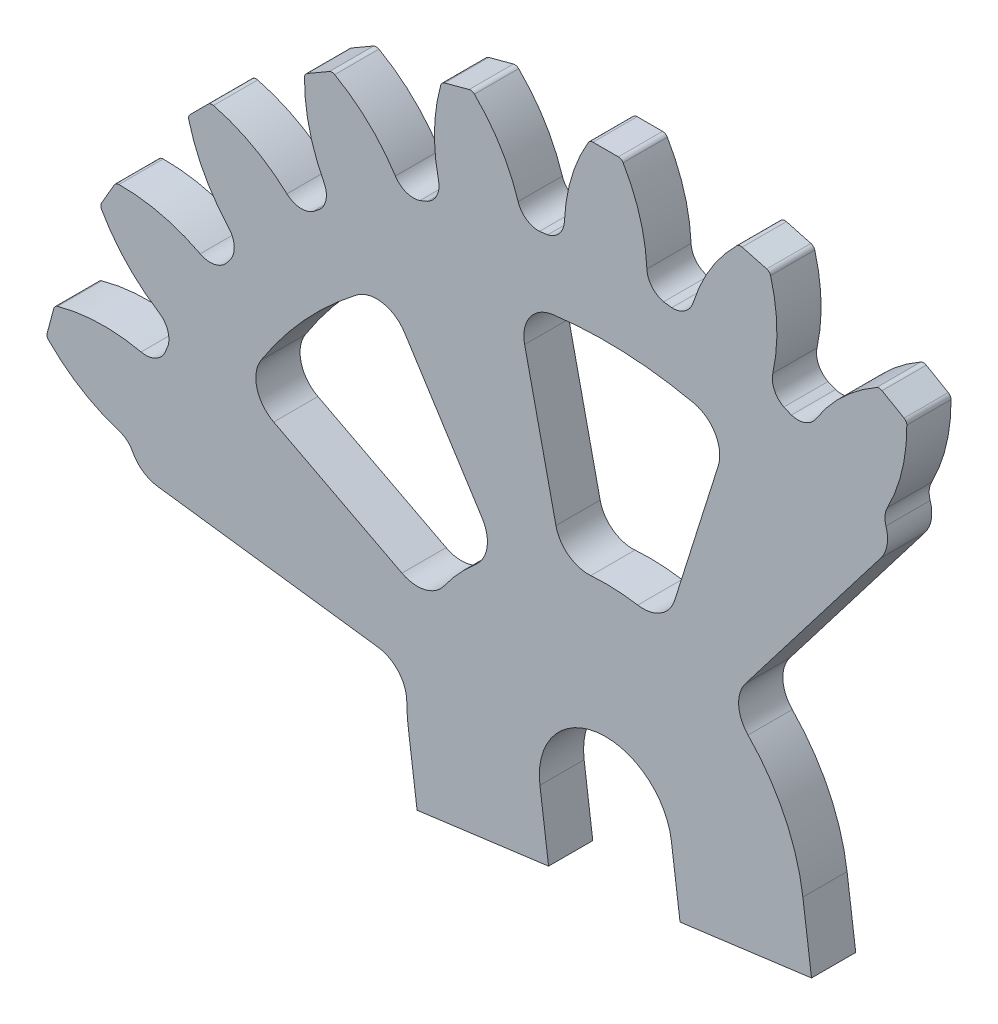
SolidWorks part; units mm, degrees
note: '?' marks a value the reader was unsure of.
ref_plane "Front" through (0, 0, 0) normal (0, 0, 1) x (1, 0, 0)
ref_plane "Top" through (0, 0, 0) normal (0, 1, 0) x (1, 0, 0)
ref_plane "Right" through (0, 0, 0) normal (1, 0, 0) x (0, 0, -1)
sketch "Sketch1" plane through (0, 0, 0) normal (0, 0, 1) x (1, 0, 0)
  line L0 (17.8313, 135.4426) -> (17.1518, 135.5303)
  line L1 (17.1518, 135.5303) -> (16.4718, 135.6147)
  line L2 (16.4718, 135.6147) -> (16.2604, 135.6453)
  line L3 (16.2604, 135.6453) -> (16.051, 135.6853)
  line L4 (16.051, 135.6853) -> (15.8446, 135.7346)
  line L5 (15.8446, 135.7346) -> (15.6419, 135.7926)
  line L6 (15.6419, 135.7926) -> (15.4439, 135.859)
  line L7 (15.4439, 135.859) -> (15.2509, 135.9332)
  line L8 (15.2509, 135.9332) -> (15.0638, 136.0145)
  line L9 (15.0638, 136.0145) -> (14.8827, 136.1025)
  line L10 (14.8827, 136.1025) -> (14.7082, 136.1963)
  line L11 (14.7082, 136.1963) -> (14.5404, 136.2955)
  line L12 (14.5404, 136.2955) -> (14.3796, 136.3992)
  line L13 (14.3796, 136.3992) -> (14.2256, 136.507)
  line L14 (14.2256, 136.507) -> (14.0785, 136.6183)
  line L15 (14.0785, 136.6183) -> (13.9383, 136.7325)
  line L16 (13.9383, 136.7325) -> (13.8047, 136.8493)
  line L17 (13.8047, 136.8493) -> (13.6777, 136.9682)
  line L18 (13.6777, 136.9682) -> (13.5568, 137.0887)
  line L19 (13.5568, 137.0887) -> (13.442, 137.2107)
  line L20 (13.442, 137.2107) -> (13.333, 137.3338)
  line L21 (13.333, 137.3338) -> (13.2295, 137.4577)
  line L22 (13.2295, 137.4577) -> (13.1311, 137.5824)
  line L23 (13.1311, 137.5824) -> (13.0378, 137.7076)
  line L24 (13.0378, 137.7076) -> (12.9491, 137.8333)
  line L25 (12.9491, 137.8333) -> (12.8649, 137.9592)
  line L26 (12.8649, 137.9592) -> (12.7848, 138.0855)
  line L27 (12.7848, 138.0855) -> (12.7088, 138.2119)
  line L28 (12.7088, 138.2119) -> (12.6364, 138.3386)
  line L29 (12.6364, 138.3386) -> (12.5676, 138.4654)
  line L30 (12.5676, 138.4654) -> (12.4399, 138.7196)
  line L31 (12.4399, 138.7196) -> (12.324, 138.9746)
  line L32 (12.324, 138.9746) -> (12.2189, 139.2306)
  line L33 (12.2189, 139.2306) -> (12.1235, 139.488)
  line L34 (12.1235, 139.488) -> (12.037, 139.7472)
  line L35 (12.037, 139.7472) -> (11.9587, 140.0083)
  line L36 (11.9587, 140.0083) -> (11.8878, 140.272)
  line L37 (11.8878, 140.272) -> (11.8239, 140.5386)
  line L38 (11.8239, 140.5386) -> (11.7667, 140.8083)
  line L39 (11.7667, 140.8083) -> (11.7159, 141.0816)
  line L40 (11.7159, 141.0816) -> (11.671, 141.3588)
  line L41 (11.671, 141.3588) -> (11.6319, 141.6402)
  line L42 (11.6319, 141.6402) -> (11.5986, 141.9261)
  line L43 (11.5986, 141.9261) -> (11.5708, 142.2169)
  line L44 (11.5708, 142.2169) -> (11.5484, 142.5127)
  line L45 (11.5484, 142.5127) -> (11.5316, 142.8138)
  line L46 (11.5316, 142.8138) -> (11.5201, 143.1205)
  line L47 (11.5201, 143.1205) -> (11.514, 143.431)
  line L48 (11.514, 143.431) -> (11.5065, 143.7657)
  line L49 (11.5065, 143.7657) -> (11.492, 144.1009)
  line L50 (11.492, 144.1009) -> (11.4715, 144.4366)
  line L51 (11.4715, 144.4366) -> (11.4457, 144.7727)
  line L52 (11.4457, 144.7727) -> (11.415, 145.1092)
  line L53 (11.415, 145.1092) -> (11.3797, 145.4459)
  line L54 (11.3797, 145.4459) -> (11.3401, 145.783)
  line L55 (11.3401, 145.783) -> (11.2966, 146.1204)
  line L56 (11.2966, 146.1204) -> (11.2492, 146.458)
  line L57 (11.2492, 146.458) -> (11.1981, 146.7959)
  line L58 (11.1981, 146.7959) -> (11.1435, 147.1341)
  line L59 (11.1435, 147.1341) -> (11.0853, 147.4724)
  line L60 (11.0853, 147.4724) -> (11.024, 147.8109)
  line L61 (11.024, 147.8109) -> (10.9594, 148.1496)
  line L62 (10.9594, 148.1496) -> (10.8916, 148.4885)
  line L63 (10.8916, 148.4885) -> (10.8208, 148.8275)
  line L64 (10.8208, 148.8275) -> (10.6703, 149.5062)
  line L65 (10.6703, 149.5062) -> (10.5084, 150.1852)
  line L66 (10.5084, 150.1852) -> (10.3354, 150.8648)
  line L67 (10.3354, 150.8648) -> (10.1517, 151.5448)
  line L68 (10.1517, 151.5448) -> (9.9576, 152.2251)
  line L69 (9.9576, 152.2251) -> (9.7535, 152.9057)
  line L70 (9.7535, 152.9057) -> (9.5395, 153.5865)
  line L71 (9.5395, 153.5865) -> (9.3158, 154.2674)
  line L72 (9.3158, 154.2674) -> (9.0828, 154.9485)
  line L73 (9.0828, 154.9485) -> (8.8405, 155.6295)
  line L74 (8.8405, 155.6295) -> (8.589, 156.3106)
  line L75 (8.589, 156.3106) -> (8.3286, 156.9917)
  line L76 (8.3286, 156.9917) -> (8.0594, 157.6726)
  line L77 (8.0594, 157.6726) -> (7.7815, 158.3534)
  line L78 (7.7815, 158.3534) -> (7.4951, 159.0339)
  line L79 (7.4951, 159.0339) -> (7.2001, 159.7142)
  line L80 (7.2001, 159.7142) -> (6.8968, 160.3942)
  line L81 (6.8968, 160.3942) -> (6.5852, 161.0739)
  line L82 (6.5852, 161.0739) -> (6.2654, 161.7531)
  line L83 (6.2654, 161.7531) -> (5.9375, 162.432)
  line L84 (5.9375, 162.432) -> (5.6015, 163.1103)
  line L85 (5.6015, 163.1103) -> (5.2576, 163.7881)
  line L86 (5.2576, 163.7881) -> (4.9057, 164.4653)
  line L87 (4.9057, 164.4653) -> (4.5461, 165.1419)
  line L88 (4.5461, 165.1419) -> (3.4097, 165.1693)
  line L89 (3.4097, 165.1693) -> (2.2732, 165.1888)
  line L90 (2.2732, 165.1888) -> (1.1366, 165.2006)
  line L91 (1.1366, 165.2006) -> (0, 165.2045)
  line L92 (0, 165.2045) -> (-1.1366, 165.2006)
  line L93 (-1.1366, 165.2006) -> (-2.2732, 165.1888)
  line L94 (-2.2732, 165.1888) -> (-3.4097, 165.1693)
  line L95 (-3.4097, 165.1693) -> (-4.5461, 165.1419)
  line L96 (-4.5461, 165.1419) -> (-4.9057, 164.4653)
  line L97 (-4.9057, 164.4653) -> (-5.2576, 163.7881)
  line L98 (-5.2576, 163.7881) -> (-5.6015, 163.1103)
  line L99 (-5.6015, 163.1103) -> (-5.9375, 162.432)
  line L100 (-5.9375, 162.432) -> (-6.2654, 161.7531)
  line L101 (-6.2654, 161.7531) -> (-6.5852, 161.0739)
  line L102 (-6.5852, 161.0739) -> (-6.8968, 160.3942)
  line L103 (-6.8968, 160.3942) -> (-7.2001, 159.7142)
  line L104 (-7.2001, 159.7142) -> (-7.4951, 159.0339)
  line L105 (-7.4951, 159.0339) -> (-7.7815, 158.3534)
  line L106 (-7.7815, 158.3534) -> (-8.0594, 157.6726)
  line L107 (-8.0594, 157.6726) -> (-8.3286, 156.9917)
  line L108 (-8.3286, 156.9917) -> (-8.589, 156.3106)
  line L109 (-8.589, 156.3106) -> (-8.8405, 155.6295)
  line L110 (-8.8405, 155.6295) -> (-9.0828, 154.9485)
  line L111 (-9.0828, 154.9485) -> (-9.3158, 154.2674)
  line L112 (-9.3158, 154.2674) -> (-9.5395, 153.5865)
  line L113 (-9.5395, 153.5865) -> (-9.7535, 152.9057)
  line L114 (-9.7535, 152.9057) -> (-9.9576, 152.2251)
  line L115 (-9.9576, 152.2251) -> (-10.1517, 151.5448)
  line L116 (-10.1517, 151.5448) -> (-10.3354, 150.8648)
  line L117 (-10.3354, 150.8648) -> (-10.5084, 150.1852)
  line L118 (-10.5084, 150.1852) -> (-10.6703, 149.5062)
  line L119 (-10.6703, 149.5062) -> (-10.8208, 148.8275)
  line L120 (-10.8208, 148.8275) -> (-10.8916, 148.4885)
  line L121 (-10.8916, 148.4885) -> (-10.9594, 148.1496)
  line L122 (-10.9594, 148.1496) -> (-11.024, 147.8109)
  line L123 (-11.024, 147.8109) -> (-11.0853, 147.4724)
  line L124 (-11.0853, 147.4724) -> (-11.1435, 147.1341)
  line L125 (-11.1435, 147.1341) -> (-11.1981, 146.7959)
  line L126 (-11.1981, 146.7959) -> (-11.2492, 146.458)
  line L127 (-11.2492, 146.458) -> (-11.2966, 146.1204)
  line L128 (-11.2966, 146.1204) -> (-11.3401, 145.783)
  line L129 (-11.3401, 145.783) -> (-11.3797, 145.4459)
  line L130 (-11.3797, 145.4459) -> (-11.415, 145.1092)
  line L131 (-11.415, 145.1092) -> (-11.4457, 144.7727)
  line L132 (-11.4457, 144.7727) -> (-11.4715, 144.4366)
  line L133 (-11.4715, 144.4366) -> (-11.492, 144.1009)
  line L134 (-11.492, 144.1009) -> (-11.5065, 143.7657)
  line L135 (-11.5065, 143.7657) -> (-11.514, 143.431)
  line L136 (-11.514, 143.431) -> (-11.5201, 143.1205)
  line L137 (-11.5201, 143.1205) -> (-11.5316, 142.8138)
  line L138 (-11.5316, 142.8138) -> (-11.5484, 142.5127)
  line L139 (-11.5484, 142.5127) -> (-11.5708, 142.2169)
  line L140 (-11.5708, 142.2169) -> (-11.5986, 141.9261)
  line L141 (-11.5986, 141.9261) -> (-11.6319, 141.6402)
  line L142 (-11.6319, 141.6402) -> (-11.671, 141.3588)
  line L143 (-11.671, 141.3588) -> (-11.7159, 141.0816)
  line L144 (-11.7159, 141.0816) -> (-11.7667, 140.8083)
  line L145 (-11.7667, 140.8083) -> (-11.8239, 140.5386)
  line L146 (-11.8239, 140.5386) -> (-11.8878, 140.272)
  line L147 (-11.8878, 140.272) -> (-11.9587, 140.0083)
  line L148 (-11.9587, 140.0083) -> (-12.037, 139.7472)
  line L149 (-12.037, 139.7472) -> (-12.1235, 139.488)
  line L150 (-12.1235, 139.488) -> (-12.2189, 139.2306)
  line L151 (-12.2189, 139.2306) -> (-12.324, 138.9746)
  line L152 (-12.324, 138.9746) -> (-12.4399, 138.7196)
  line L153 (-12.4399, 138.7196) -> (-12.5676, 138.4654)
  line L154 (-12.5676, 138.4654) -> (-12.6364, 138.3386)
  line L155 (-12.6364, 138.3386) -> (-12.7088, 138.2119)
  line L156 (-12.7088, 138.2119) -> (-12.7848, 138.0855)
  line L157 (-12.7848, 138.0855) -> (-12.8649, 137.9592)
  line L158 (-12.8649, 137.9592) -> (-12.9491, 137.8333)
  line L159 (-12.9491, 137.8333) -> (-13.0378, 137.7076)
  line L160 (-13.0378, 137.7076) -> (-13.1311, 137.5824)
  line L161 (-13.1311, 137.5824) -> (-13.2295, 137.4577)
  line L162 (-13.2295, 137.4577) -> (-13.333, 137.3338)
  line L163 (-13.333, 137.3338) -> (-13.442, 137.2107)
  line L164 (-13.442, 137.2107) -> (-13.5568, 137.0887)
  line L165 (-13.5568, 137.0887) -> (-13.6777, 136.9682)
  line L166 (-13.6777, 136.9682) -> (-13.8047, 136.8493)
  line L167 (-13.8047, 136.8493) -> (-13.9383, 136.7325)
  line L168 (-13.9383, 136.7325) -> (-14.0785, 136.6183)
  line L169 (-14.0785, 136.6183) -> (-14.2256, 136.507)
  line L170 (-14.2256, 136.507) -> (-14.3796, 136.3992)
  line L171 (-14.3796, 136.3992) -> (-14.5404, 136.2955)
  line L172 (-14.5404, 136.2955) -> (-14.7082, 136.1963)
  line L173 (-14.7082, 136.1963) -> (-14.8827, 136.1025)
  line L174 (-14.8827, 136.1025) -> (-15.0638, 136.0145)
  line L175 (-15.0638, 136.0145) -> (-15.2509, 135.9332)
  line L176 (-15.2509, 135.9332) -> (-15.4439, 135.859)
  line L177 (-15.4439, 135.859) -> (-15.6419, 135.7926)
  line L178 (-15.6419, 135.7926) -> (-15.8446, 135.7346)
  line L179 (-15.8446, 135.7346) -> (-16.051, 135.6853)
  line L180 (-16.051, 135.6853) -> (-16.2604, 135.6453)
  line L181 (-16.2604, 135.6453) -> (-16.4718, 135.6147)
  line L182 (-16.4718, 135.6147) -> (-17.1518, 135.5303)
  line L183 (-17.1518, 135.5303) -> (-17.8313, 135.4426)
sketch "Sketch2" plane through (0, 0, 0) normal (0, 0, 1) x (1, 0, 0)
  line L0 (0, 0) -> (0, 362.4864) construction
  line L1 (-4.5461, 165.1419) -> (4.5461, 165.1419)
  line L2 (-17.8314, 135.4426) -> (0, 0) construction
  line L3 (17.8314, 135.4426) -> (17.8314, 110.0426)
  line L4 (17.8314, 110.0426) -> (-17.8314, 110.0426)
  line L5 (-17.8314, 110.0426) -> (-17.8314, 135.4426)
  line L6 (-17.1518, 135.5303) -> (-17.8313, 135.4426) construction
  arc A0 (-17.8314, 135.4426) -> (-11.8464, 141.3588) centre (-18.0264, 141.6253) ccw
  arc A1 (-11.8464, 141.3588) -> (-4.5461, 165.1419) centre (37.4738, 139.2317) cw
  arc A2 (11.8464, 141.3588) -> (4.5461, 165.1419) centre (-37.4738, 139.2317) ccw
  arc A3 (17.8314, 135.4426) -> (11.8464, 141.3588) centre (18.0264, 141.6253) cw
  point P25 (0, 165.1419)
  dimension "D1" = 7.5
  dimension "D2" = 25.4
sketch "Sketch3" plane through (0, 0, 0) normal (0, 0, 1) x (1, 0, 0)
  circle A0 centre (0, 0) radius 136.6114
extrude "Extrude1" add sketch "Sketch3" along normal blind 12.7
extrude "Extrude2" add sketch "Sketch2" along normal blind 12.7
fillet "Fillet2" radius 1.5875 2 edges at (4.5461, 165.1419, 6.35) (-4.5461, 165.1419, 6.35)
ref_axis "Axis1" through (0, 0, 12.7) along (0, 0, -1)?
pattern_circular "CirPattern1" count 24 over 360 about axis through (0, 0, 0) along (0, 0, 1) of "Extrude2", "Fillet2"
sketch "Sketch4" plane through (0, 0, 0) normal (0, 0, 1) x (1, 0, 0)
  line L0 (-268.2184, 35.3116) -> (0, 0)
  line L1 (0, 0) -> (164.69, 214.6281)
  line L4 (0, -6.985) -> (0, 6.985) construction
  arc A0 (164.69, 214.6281) -> (-268.2184, 35.3116) centre (0, 0) ccw construction
  dimension "D1" = 37.5
  dimension "D2" = 82.5
  dimension "D3" = 120
extrude "Cut-Extrude1" cut sketch "Sketch4" against normal through all and the other way through all flip side to cut
sketch "Sketch5" plane through (0, 0, 0) normal (0, 0, 1) x (1, 0, 0)
  circle A0 centre (0, 0) radius 19.05
  dimension "D1" = 38.1
extrude "Cut-Extrude2" cut sketch "Sketch5" along normal up to next
sketch "Sketch6" plane through (0, 0, 0) normal (0, 0, 1) x (1, 0, 0)
  line L0 (-18.887, -2.4865) -> (-16.4005, -21.3735)
  line L1 (-18.887, 2.4865) -> (-135.4426, 17.8314) construction
  line L2 (-16.4005, -21.3735) -> (-54.1745, -26.3466)
  line L3 (83.1637, 108.3811) -> (11.5969, 15.1134) construction
  line L4 (-56.6611, 7.4596) -> (-18.887, 2.4865)
  line L5 (11.5969, 15.1134) -> (34.7907, 45.3401)
  line L6 (-54.1745, -26.3466) -> (59.1476, -11.4275) construction
  line L7 (-56.6611, -7.4596) -> (-54.1745, -26.3466)
  line L8 (56.6611, 7.4596) -> (59.1476, -11.4275)
  line L9 (18.887, 2.4865) -> (21.3735, -16.4005)
  line L10 (21.3735, -16.4005) -> (59.1476, -11.4275)
  line L11 (-56.6611, -7.4596) -> (56.6611, 7.4596) construction
  circle A0 centre (0, 0) radius 19.05 construction
  arc A1 (-56.6611, -7.4596) -> (-56.6611, 7.4596) centre (0, 0) cw
  arc A2 (-18.887, -2.4865) -> (-18.887, 2.4865) centre (0, 0) cw
  arc A3 (11.5969, 15.1134) -> (-18.887, 2.4865) centre (0, 0) ccw construction
  arc A4 (56.6611, 7.4596) -> (34.7907, 45.3401) centre (0, 0) ccw
  arc A5 (18.887, 2.4865) -> (11.5969, 15.1134) centre (0, 0) ccw
  dimension "D1" = 38.1
  dimension "D2" = 15
extrude "Extrude3" add sketch "Sketch6" along normal blind 12.7
sketch "Sketch8" plane through (0, 0, 0) normal (0, 0, 1) x (1, 0, 0)
  line L0 (0, 0) -> (-104.2016, 54.2439) construction
  line L1 (0, 0) -> (35.3254, 112.0379) construction
  line L2 (-56.6611, 7.4596) -> (-135.4426, 17.8314) construction
  line L3 (83.1637, 108.3811) -> (34.7907, 45.3401) construction
  line L4 (-25.4262, 114.6904) -> (-12.3695, 55.7953)
  line L5 (-63.1193, 99.0774) -> (-30.7067, 48.1998)
  line L6 (-104.2016, 54.2439) -> (-50.6927, 26.3889)
  line L7 (35.3254, 112.0379) -> (17.1853, 54.5049)
  arc A0 (-50.6927, 26.3889) -> (17.1853, 54.5049) centre (0, 0) cw construction
  arc A1 (-104.2016, 54.2439) -> (35.3254, 112.0379) centre (0, 0) cw construction
  arc A2 (56.6611, 7.4596) -> (34.7907, 45.3401) centre (0, 0) ccw construction
  arc A3 (-50.6927, 26.3889) -> (-30.7067, 48.1998) centre (0, 0) cw
  arc A4 (17.1853, 54.5049) -> (-12.3695, 55.7953) centre (0, 0) ccw
  arc A5 (35.3254, 112.0379) -> (-25.4262, 114.6904) centre (0, 0) ccw
  arc A6 (-104.2016, 54.2439) -> (-63.1193, 99.0774) centre (0, 0) cw
  dimension "D3" = 117.475
  dimension "D1" = 20
  dimension "D2" = 20
  dimension "D5" = 30
  dimension "D6" = 30
  dimension "D7" = 20
extrude "Cut-Extrude5" cut sketch "Sketch8" along normal through all
fillet "Fillet1" radius 9.525 10 edges at (34.7907, 45.3401, 6.35) (-50.6927, 26.3889, 6.35) (-30.7067, 48.1998, 6.35) (-63.1193, 99.0774, 6.35) (-104.2016, 54.2439, 6.35) (-12.3695, 55.7953, 6.35) (17.1853, 54.5049, 6.35) (35.3254, 112.0379, 6.35) (-25.4262, 114.6904, 6.35) (-56.6611, 7.4596, 6.35)
sketch "Sketch9" plane through (0, 0, 0) normal (0, 0, 1) x (1, 0, 0)
  line L0 (83.1637, 108.3811) -> (40.1729, 52.3543) construction
  line L1 (79.0341, 102.9992) -> (83.8095, 109.2227)
  line L2 (80.5391, 111.7322) -> (83.8095, 109.2227)
  line L3 (-65.4266, 8.6136) -> (-135.4426, 17.8314) construction
  line L4 (-128.717, 16.9459) -> (-136.4944, 17.9698)
  line L5 (-135.9563, 22.0568) -> (-136.4944, 17.9698)
  arc A0 (79.0341, 102.9992) -> (80.5391, 111.7322) centre (71.4774, 108.7977) ccw
  arc A1 (80.9387, 116.4971) -> (82.229, 109.0919) centre (86.424, 113.6379) ccw construction
  arc A2 (-135.9563, 22.0568) -> (-128.717, 16.9459) centre (-127.4737, 26.3894) ccw
  arc A3 (-135.2843, 18.995) -> (-139.6082, 25.1436) centre (-141.4651, 19.2431) ccw construction
  dimension "D1" = 9.525
  dimension "D2" = 9.525
extrude "Cut-Extrude7" cut sketch "Sketch9" along normal blind 12.7
